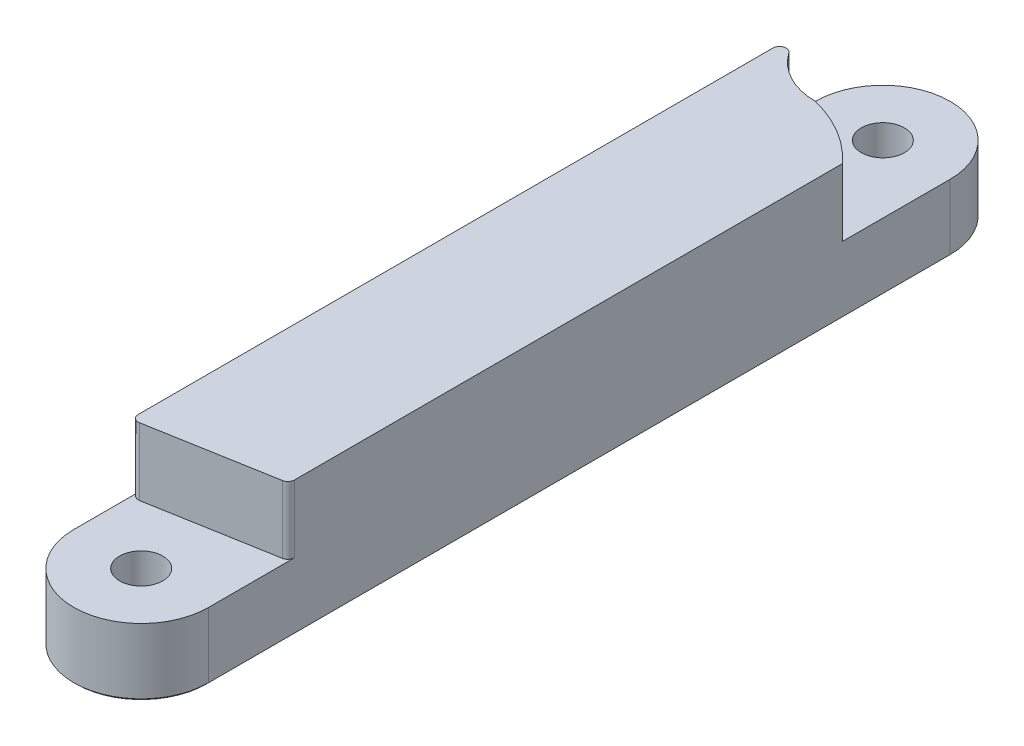
SolidWorks part; units mm, degrees
ref_plane "Front Plane" through (0, 0, 0) normal (0, 0, 1) x (1, 0, 0)
ref_plane "Top Plane" through (0, 0, 0) normal (0, 1, 0) x (1, 0, 0)
ref_plane "Right Plane" through (0, 0, 0) normal (1, 0, 0) x (0, 0, -1)
other "Configuration Table"
sketch "complete_sketch" plane through (0, 0, 0) normal (0, 1, 0) x (1, 0, 0)
  line L0 (0, 0) -> (0, 55) construction
  line L1 (-5, 0) -> (-5, 55)
  line L2 (5, 0) -> (5, 55)
  line L3 (5, 5.9588) -> (-5, 4.1955)
  line L4 (-5, 4.1955) -> (-5, 52.7087)
  line L5 (5, 5.9588) -> (5, 52.7087)
  line L6 (-5, 47) -> (5, 47)
  arc A0 (-5, 0) -> (5, 0) centre (0, 0) ccw
  arc A1 (5, 55) -> (-5, 55) centre (0, 55) ccw
  circle A2 centre (0, 55) radius 1.6
  circle A3 centre (0, 0) radius 1.6
  circle A5 centre (0, 0) radius 5 construction
  circle A6 centre (0, 55) radius 5 construction
  point P3 (0, 27.5)
  dimension "D2" = 3.2
  dimension "D5" = 8
  dimension "D1" = 10
  dimension "D3" = 55
  dimension "D4" = 80
extrude "center_body" add sketch "complete_sketch" along normal blind 10 contours L6 L1 L3 L2 region at (-0.035, 0, -26.0355)
extrude "connector_body" add sketch "Sketch1<3>" along normal blind 5 contours L1 A0 L2 L3 A3 | L1 L2 A1 A2 region at (-4.8516, 0, -2.0977) region at (0, 0, -52.8722)
sketch "Sketch1<3>" plane through (0, 0, 0) normal (0, 1, 0) x (1, 0, 0) same geometry as "complete_sketch"
sketch "Sketch1" [suppressed] plane through (0, 5, 0) normal (0, 1, 0) x (1, 0, 0)
  line L0 (-5, 47) -> (5, 47)
  line L1 (5, 47) -> (5, 55)
  circle A0 centre (0, 55) radius 5 construction
  arc A1 (5, 55) -> (0, 50) centre (0, 55) cw
  arc A2 (0, 50) -> (-5, 47) centre (2.4214, 40.2976) ccw
  dimension "D1" = 10
extrude "mech_lock_left" [suppressed] add sketch "Sketch1" along normal blind 5
sketch "Sketch2" plane through (0, 5, 0) normal (0, 1, 0) x (1, 0, 0)
  line L0 (5, 47) -> (-5, 47)
  line L1 (-5, 47) -> (-5, 55)
  circle A0 centre (0, 55) radius 5 construction
  arc A1 (-5, 55) -> (0, 50) centre (0, 55) ccw
  arc A2 (0, 50) -> (5, 47) centre (-2.4214, 40.2976) cw
  dimension "D1" = 10
  dimension "D2" = 10
extrude "mech_lock_right" add sketch "Sketch2" along normal blind 5
fillet "dulling_fillet_general" radius 0.5 2 edges at (5, 7.5, -5.9588) (-5, 7.5, -4.1955)
chamfer "elephantsfoot_compensation" distance 0.16 angle 45 6 edges at (0, 0, -53.4) (0, 0, 1.6) (0, 0, 5) (0, 0, -60) (5, 0, -27.5) (-5, 0, -27.5)
fillet "dulling_fillet_left" [suppressed] radius 0.5
fillet "dulling_fillet_right" radius 0.5 1 edges at (-5, 7.5, -55)
